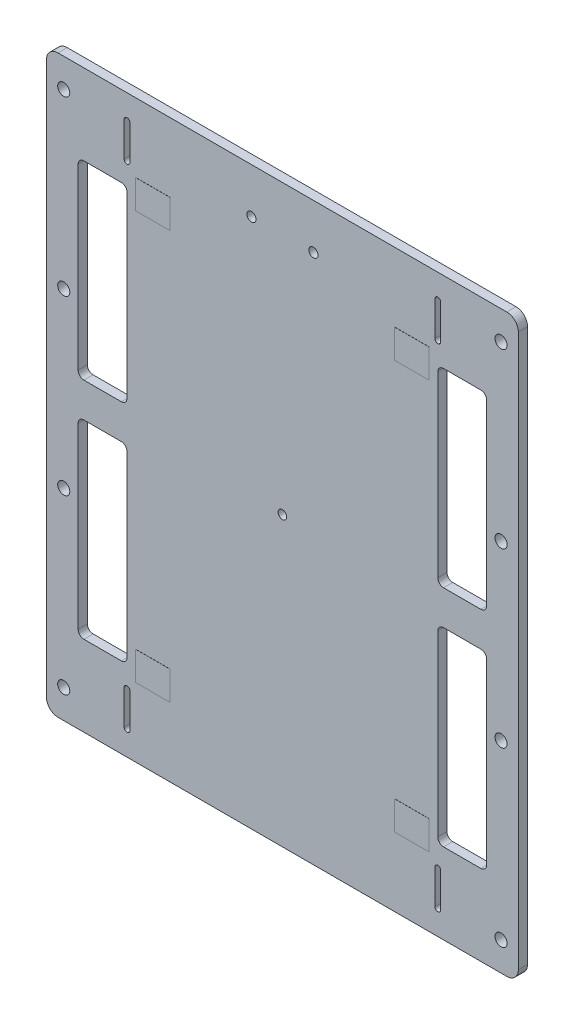
SolidWorks part; units mm, degrees
material "Oshpark board"
ref_plane "Front Plane" through (0, 0, 0) normal (0, 0, 1) x (1, 0, 0)
ref_plane "Top Plane" through (0, 0, 0) normal (0, 1, 0) x (1, 0, 0)
ref_plane "Right Plane" through (0, 0, 0) normal (1, 0, 0) x (0, 0, -1)
sketch "Sketch1" plane through (0, 0, 0) normal (0, 0, 1) x (1, 0, 0)
  line L1 (-39, -50) -> (39, -50)
  line L2 (-41, -48) -> (-41, 48)
  line L3 (-39, 50) -> (39, 50)
  line L4 (41, -48) -> (41, 48)
  line L5 (-41, -50) -> (41, 50) construction
  line L6 (-41, 50) -> (41, -50) construction
  arc A0 (-39, -50) -> (-41, -48) centre (-39, -48) cw
  arc A1 (39, -50) -> (41, -48) centre (39, -48) ccw
  arc A2 (39, 50) -> (41, 48) centre (39, 48) cw
  arc A3 (-41, 48) -> (-39, 50) centre (-39, 48) cw
  point P0 (0, 0)
  dimension "D3" = 2
  dimension "D1" = 100
  dimension "D2" = 82
extrude "Boss-Extrude1" add sketch "Sketch1" along normal blind 1.6
sketch "Sketch2" plane through (0, 0, 1.6) normal (0, 0, 1) x (1, 0, 0)
  line L0 (39, 50) -> (-39, 50) construction
  line L1 (-41, 48) -> (-41, -48) construction
  line L3 (-37.5, 44.2) -> (-37.5, 4.2) construction
  circle A0 centre (0, 0) radius 0.75
  circle A1 centre (-37.5, 44.2) radius 1.05 construction
  circle A2 centre (37.5, 44.2) radius 1.05 construction
  circle A3 centre (37.5, 4.2) radius 1.05 construction
  circle A4 centre (37.5, -35.8) radius 1.05 construction
  circle A5 centre (-37.5, 4.2) radius 1.05 construction
  circle A6 centre (-37.5, -35.8) radius 1.05 construction
  circle A7 centre (-5.38, 42.15) radius 0.8
  circle A8 centre (5.39, 42.15) radius 0.8
  dimension "D1" = 1.5
  dimension "D2" = 2.1
  dimension "D9" = 10.77
  dimension "D7" = 1.6
  dimension "D11" = 7.85
  dimension "D12" = 35.62
  dimension "D3" = 5.8
  dimension "D4" = 3.5
  dimension "D8" = 40
  dimension "D10" = 37.5
  dimension "D5" = 2
  dimension "D6" = 3
extrude "Cut-Extrude1" cut sketch "Sketch2" against normal through all
sketch "Sketch4" plane through (0, 0, 1.6) normal (0, 0, 1) x (1, 0, 0)
  line L0 (-27, 39.75) -> (-27, 45.75) construction
  line L1 (-27.5, 39.75) -> (-27.5, 45.75)
  line L2 (-26.5, 39.75) -> (-26.5, 45.75)
  line L3 (39, 50) -> (-39, 50) construction
  line L4 (-41, 48) -> (-41, -48) construction
  line L5 (27, 39.75) -> (27, 45.75) construction
  line L6 (26.5, 39.75) -> (26.5, 45.75)
  line L7 (27.5, 39.75) -> (27.5, 45.75)
  line L8 (27, -45.75) -> (27, -39.75) construction
  line L9 (26.5, -45.75) -> (26.5, -39.75)
  line L10 (27.5, -45.75) -> (27.5, -39.75)
  line L11 (-27, -45.75) -> (-27, -39.75) construction
  line L12 (-27.5, -45.75) -> (-27.5, -39.75)
  line L13 (-26.5, -45.75) -> (-26.5, -39.75)
  line L14 (-27, 39.75) -> (27, 39.75) construction
  line L15 (-39, -50) -> (39, -50) construction
  arc A0 (-27.5, 39.75) -> (-26.5, 39.75) centre (-27, 39.75) ccw
  arc A1 (-26.5, 45.75) -> (-27.5, 45.75) centre (-27, 45.75) ccw
  arc A2 (26.5, 39.75) -> (27.5, 39.75) centre (27, 39.75) ccw
  arc A3 (27.5, 45.75) -> (26.5, 45.75) centre (27, 45.75) ccw
  arc A4 (26.5, -45.75) -> (27.5, -45.75) centre (27, -45.75) ccw
  arc A5 (27.5, -39.75) -> (26.5, -39.75) centre (27, -39.75) ccw
  arc A6 (-27.5, -45.75) -> (-26.5, -45.75) centre (-27, -45.75) ccw
  arc A7 (-26.5, -39.75) -> (-27.5, -39.75) centre (-27, -39.75) ccw
  point P2 (-27, 42.75)
  point P16 (27, 42.75)
  point P23 (27, -42.75)
  point P30 (-27, -42.75)
  dimension "D1" = 4.25
  dimension "D2" = 13.5
  dimension "D3" = 1
  dimension "D4" = 6
  dimension "D7" = 54
  dimension "D8" = 14
  dimension "D9" = 4.25
  dimension "D10" = 4.25
  dimension "D5" = 2
  dimension "D6" = 2
extrude "Cut-Extrude3" cut sketch "Sketch4" against normal blind 1.6
sketch "Sketch3" plane through (0, 0, 1.6) normal (0, 0, 1) x (1, 0, 0)
  line L1 (-34.5, 36) -> (-28, 36)
  line L2 (-35.5, 35) -> (-35.5, 4)
  line L3 (-34.5, 3) -> (-28, 3)
  line L4 (-27, 35) -> (-27, 4)
  line L5 (-41, 48) -> (-41, -48) construction
  line L6 (41, 0) -> (-41, 0) construction
  line L7 (41, -48) -> (41, 48) construction
  line L8 (-41, 48) -> (-41, -48) construction
  line L9 (0, 50) -> (0, -50) construction
  line L10 (39, 50) -> (-39, 50) construction
  line L11 (-39, -50) -> (39, -50) construction
  line L12 (-34.5, -36) -> (-28, -36)
  line L13 (-35.5, -35) -> (-35.5, -4)
  line L14 (-34.5, -3) -> (-28, -3)
  line L15 (-27, -35) -> (-27, -4)
  line L16 (34.5, -36) -> (28, -36)
  line L17 (27, -35) -> (27, -4)
  line L18 (34.5, -3) -> (28, -3)
  line L20 (35.5, -35) -> (35.5, -4)
  line L21 (34.5, 36) -> (28, 36)
  line L22 (35.5, 35) -> (35.5, 4)
  line L23 (34.5, 3) -> (28, 3)
  line L24 (27, 35) -> (27, 4)
  arc A0 (-35.5, 4) -> (-34.5, 3) centre (-34.5, 4) ccw
  arc A1 (-28, 3) -> (-27, 4) centre (-28, 4) ccw
  arc A2 (-28, 36) -> (-27, 35) centre (-28, 35) cw
  arc A3 (-34.5, 36) -> (-35.5, 35) centre (-34.5, 35) ccw
  arc A5 (-28, -36) -> (-27, -35) centre (-28, -35) ccw
  arc A6 (-34.5, -36) -> (-35.5, -35) centre (-34.5, -35) cw
  arc A7 (-35.5, -4) -> (-34.5, -3) centre (-34.5, -4) cw
  arc A8 (-28, -3) -> (-27, -4) centre (-28, -4) cw
  arc A9 (34.5, -36) -> (35.5, -35) centre (34.5, -35) ccw
  arc A10 (28, -36) -> (27, -35) centre (28, -35) cw
  arc A11 (28, -3) -> (27, -4) centre (28, -4) ccw
  arc A12 (35.5, -4) -> (34.5, -3) centre (34.5, -4) ccw
  arc A13 (28, 36) -> (27, 35) centre (28, 35) ccw
  arc A14 (34.5, 36) -> (35.5, 35) centre (34.5, 35) cw
  arc A15 (35.5, 4) -> (34.5, 3) centre (34.5, 4) cw
  arc A16 (28, 3) -> (27, 4) centre (28, 4) cw
  point P12 (-27, 3)
  point P15 (-27, 36)
  point P18 (-35.5, 36)
  dimension "D5" = 1
  dimension "D1" = 8.5
  dimension "D2" = 33
  dimension "D3" = 14
  dimension "D4" = 5.5
extrude "Cut-Extrude2" cut sketch "Sketch3" against normal through all
sketch "Sketch5" plane through (0, 0, 1.6) normal (0, 0, 1) x (1, 0, 0)
  line L0 (-41, 48) -> (-41, -48) construction
  line L1 (-25.5, 38) -> (-19.5, 38)
  line L2 (-25.5, 38) -> (-25.5, 33)
  line L3 (-25.5, 33) -> (-19.5, 33)
  line L4 (-19.5, 38) -> (-19.5, 33)
  line L5 (39, 50) -> (-39, 50) construction
  line L6 (19.5, 38) -> (19.5, 33)
  line L7 (25.5, 38) -> (25.5, 33)
  line L8 (19.5, 33) -> (25.5, 33)
  line L9 (19.5, 38) -> (25.5, 38)
  line L10 (19.5, -33) -> (19.5, -38)
  line L11 (25.5, -33) -> (25.5, -38)
  line L12 (19.5, -38) -> (25.5, -38)
  line L13 (19.5, -33) -> (25.5, -33)
  line L14 (-25.5, -33) -> (-25.5, -38)
  line L15 (-19.5, -33) -> (-19.5, -38)
  line L16 (-25.5, -38) -> (-19.5, -38)
  line L17 (-25.5, -33) -> (-19.5, -33)
  line L18 (-25.5, 38) -> (19.5, 38) construction
  line L19 (-25.5, 38) -> (-25.5, -33) construction
  dimension "D1" = 5
  dimension "D2" = 6
  dimension "D3" = 15.5
  dimension "D4" = 12
  dimension "D7" = 45
  dimension "D8" = 71
  dimension "D5" = 2
  dimension "D6" = 2
extrude "Boss-Extrude2" add sketch "Sketch5" along normal blind 0.02
hole_wizard "M2 Clearance Hole1" positions "Sketch6" profile "Sketch7" hole size "M2" standard "ANSI Metric" end condition through all
sketch "Sketch6" plane through (0, 0, 0) normal (0, 0, -1) x (-1, 0, 0)
  line L4 (0, -40.934) -> (0, 34.4116) construction
  line L5 (-38, -50) -> (-38, -45) construction
  line L6 (39, -50) -> (-39, -50) construction
  line L7 (-38, -45) -> (-38, -15) construction
  line L8 (-38, -15) -> (-38, 15) construction
  line L9 (-38, 15) -> (-38, 45) construction
  line L10 (-38, 45) -> (-38, 50) construction
  line L11 (-39, 50) -> (39, 50) construction
  line L13 (-41, -48) -> (-41, 48) construction
  point P0 (-38, 45)
  point P27 (-38, -15)
  point P36 (-38, -45)
  point P38 (-38, 15)
  point P58 (0, 0)
  point P59 (38, -45)
  point P60 (38, -15)
  point P61 (38, 15)
  point P62 (38, 45)
  point P63 (-37.5, 37.6723)
  point P64 (-37.5, -35.4835)
  point P65 (-37.5, -43.3994)
  dimension "D1" = 3
  dimension "D2" = 5
sketch "Sketch7" plane through (38, 45, 0) normal (1, 0, 0) x (0, 1, 0)
  line L0 (0, 0) -> (0, 1.62)
  line L1 (0, 1.62) -> (1.05, 1.62)
  line L2 (1.05, 1.62) -> (1.05, 0)
  line L5 (1.05, 0) -> (0, 0)
  line L11 (0, -6.35) -> (0, 107.95) construction
  dimension "Thru Hole Dia." = 2.1
  dimension "Thru Hole Depth" = 1.62
sketch "Sketch8" plane through (0, 0, 1.6) normal (0, 0, 1) x (1, 0, 0)
  line L0 (-15, -11.3) -> (-15, 19.7)
  line L1 (-15, -11.3) -> (-15, 19.7)
  line L2 (12, -14.3) -> (-12, -14.3)
  line L3 (12, -14.3) -> (-12, -14.3)
  line L4 (15, 19.7) -> (15, -11.3)
  line L5 (15, 19.7) -> (15, -11.3)
  line L6 (-12, 22.7) -> (12, 22.7)
  line L7 (-12, 22.7) -> (12, 22.7)
  line L8 (-32.5, 22.7) -> (-21, 22.7)
  line L9 (-32.5, 22.7) -> (-21, 22.7)
  line L10 (-35.5, 19.7) -> (-35.5, -11.3)
  line L11 (-35.5, 19.7) -> (-35.5, -11.3)
  line L12 (-21, -14.3) -> (-32.5, -14.3)
  line L13 (-21, -14.3) -> (-32.5, -14.3)
  line L14 (-18, 19.7) -> (-18, -11.3)
  line L15 (-18, 19.7) -> (-18, -11.3)
  line L16 (18, -11.3) -> (18, 19.7)
  line L17 (18, -11.3) -> (18, 19.7)
  line L18 (32.5, -14.3) -> (21, -14.3)
  line L19 (32.5, -14.3) -> (21, -14.3)
  line L20 (35.5, -11.3) -> (35.5, 19.7)
  line L21 (35.5, -11.3) -> (35.5, 19.7)
  line L22 (21, 22.7) -> (32.5, 22.7)
  line L23 (21, 22.7) -> (32.5, 22.7)
  line L24 (-15, -43) -> (-15, -20.3)
  line L25 (-15, -43) -> (-15, -20.3)
  line L26 (12, -46) -> (-12, -46)
  line L27 (12, -46) -> (-12, -46)
  line L28 (15, -20.3) -> (15, -43)
  line L29 (15, -20.3) -> (15, -43)
  line L30 (-12, -17.3) -> (12, -17.3)
  line L31 (-12, -17.3) -> (12, -17.3)
  line L32 (-35.5, -20.3) -> (-35.5, -43)
  line L33 (-35.5, -20.3) -> (-35.5, -43)
  line L34 (-32.5, -17.3) -> (-21, -17.3)
  line L35 (-32.5, -17.3) -> (-21, -17.3)
  line L36 (-18, -20.3) -> (-18, -43)
  line L37 (-18, -20.3) -> (-18, -43)
  line L38 (-21, -46) -> (-32.5, -46)
  line L39 (-21, -46) -> (-32.5, -46)
  line L40 (18, -43) -> (18, -20.3)
  line L41 (18, -43) -> (18, -20.3)
  line L42 (32.5, -46) -> (21, -46)
  line L43 (32.5, -46) -> (21, -46)
  line L44 (35.5, -43) -> (35.5, -20.3)
  line L45 (35.5, -43) -> (35.5, -20.3)
  line L46 (21, -17.3) -> (32.5, -17.3)
  line L47 (21, -17.3) -> (32.5, -17.3)
  line L48 (-15, 28.7) -> (-15, 42)
  line L49 (-15, 28.7) -> (-15, 42)
  line L50 (12, 25.7) -> (-12, 25.7)
  line L51 (12, 25.7) -> (-12, 25.7)
  line L52 (15, 42) -> (15, 28.7)
  line L53 (15, 42) -> (15, 28.7)
  line L54 (12, 45) -> (-12, 45)
  line L55 (12, 45) -> (-12, 45)
  line L56 (-35.5, 42) -> (-35.5, 28.7)
  line L57 (-35.5, 42) -> (-35.5, 28.7)
  line L58 (-21, 25.7) -> (-32.5, 25.7)
  line L59 (-21, 25.7) -> (-32.5, 25.7)
  line L60 (-18, 42) -> (-18, 28.7)
  line L61 (-18, 42) -> (-18, 28.7)
  line L62 (-21, 45) -> (-32.5, 45)
  line L63 (-21, 45) -> (-32.5, 45)
  line L64 (18, 28.7) -> (18, 42)
  line L65 (18, 28.7) -> (18, 42)
  line L66 (32.5, 25.7) -> (21, 25.7)
  line L67 (32.5, 25.7) -> (21, 25.7)
  line L68 (35.5, 28.7) -> (35.5, 42)
  line L69 (35.5, 28.7) -> (35.5, 42)
  line L70 (32.5, 45) -> (21, 45)
  line L71 (32.5, 45) -> (21, 45)
  line L72 (-32.5, -49) -> (-21, -49)
  line L73 (-32.5, -49) -> (-21, -49)
  line L74 (-12, -49) -> (12, -49)
  line L75 (-12, -49) -> (12, -49)
  line L76 (21, -49) -> (32.5, -49)
  line L77 (21, -49) -> (32.5, -49)
  line L78 (-39, -50) -> (39, -50) construction
  line L79 (41, -48) -> (41, 48) construction
  line L80 (39, 50) -> (-39, 50) construction
  line L81 (-41, 48) -> (-41, -48) construction
  line L82 (-39, -50) -> (39, -50)
  line L83 (41, -48) -> (41, 48)
  line L84 (39, 50) -> (-39, 50)
  line L85 (-41, 48) -> (-41, -48)
  arc A0 (-15, -11.3) -> (-12, -14.3) centre (-12, -11.3) ccw
  arc A1 (-15, -11.3) -> (-12, -14.3) centre (-12, -11.3) ccw
  arc A2 (12, -14.3) -> (15, -11.3) centre (12, -11.3) ccw
  arc A3 (12, -14.3) -> (15, -11.3) centre (12, -11.3) ccw
  arc A4 (15, 19.7) -> (12, 22.7) centre (12, 19.7) ccw
  arc A5 (15, 19.7) -> (12, 22.7) centre (12, 19.7) ccw
  arc A6 (-12, 22.7) -> (-15, 19.7) centre (-12, 19.7) ccw
  arc A7 (-12, 22.7) -> (-15, 19.7) centre (-12, 19.7) ccw
  arc A8 (-18, 19.7) -> (-21, 22.7) centre (-21, 19.7) ccw
  arc A9 (-18, 19.7) -> (-21, 22.7) centre (-21, 19.7) ccw
  arc A10 (-32.5, 22.7) -> (-35.5, 19.7) centre (-32.5, 19.7) ccw
  arc A11 (-32.5, 22.7) -> (-35.5, 19.7) centre (-32.5, 19.7) ccw
  arc A12 (-35.5, -11.3) -> (-32.5, -14.3) centre (-32.5, -11.3) ccw
  arc A13 (-35.5, -11.3) -> (-32.5, -14.3) centre (-32.5, -11.3) ccw
  arc A14 (-21, -14.3) -> (-18, -11.3) centre (-21, -11.3) ccw
  arc A15 (-21, -14.3) -> (-18, -11.3) centre (-21, -11.3) ccw
  arc A16 (18, -11.3) -> (21, -14.3) centre (21, -11.3) ccw
  arc A17 (18, -11.3) -> (21, -14.3) centre (21, -11.3) ccw
  arc A18 (32.5, -14.3) -> (35.5, -11.3) centre (32.5, -11.3) ccw
  arc A19 (32.5, -14.3) -> (35.5, -11.3) centre (32.5, -11.3) ccw
  arc A20 (35.5, 19.7) -> (32.5, 22.7) centre (32.5, 19.7) ccw
  arc A21 (35.5, 19.7) -> (32.5, 22.7) centre (32.5, 19.7) ccw
  arc A22 (21, 22.7) -> (18, 19.7) centre (21, 19.7) ccw
  arc A23 (21, 22.7) -> (18, 19.7) centre (21, 19.7) ccw
  arc A24 (-15, -43) -> (-12, -46) centre (-12, -43) ccw
  arc A25 (-15, -43) -> (-12, -46) centre (-12, -43) ccw
  arc A26 (12, -46) -> (15, -43) centre (12, -43) ccw
  arc A27 (12, -46) -> (15, -43) centre (12, -43) ccw
  arc A28 (15, -20.3) -> (12, -17.3) centre (12, -20.3) ccw
  arc A29 (15, -20.3) -> (12, -17.3) centre (12, -20.3) ccw
  arc A30 (-12, -17.3) -> (-15, -20.3) centre (-12, -20.3) ccw
  arc A31 (-12, -17.3) -> (-15, -20.3) centre (-12, -20.3) ccw
  arc A32 (-32.5, -17.3) -> (-35.5, -20.3) centre (-32.5, -20.3) ccw
  arc A33 (-32.5, -17.3) -> (-35.5, -20.3) centre (-32.5, -20.3) ccw
  arc A34 (-18, -20.3) -> (-21, -17.3) centre (-21, -20.3) ccw
  arc A35 (-18, -20.3) -> (-21, -17.3) centre (-21, -20.3) ccw
  arc A36 (-21, -46) -> (-18, -43) centre (-21, -43) ccw
  arc A37 (-21, -46) -> (-18, -43) centre (-21, -43) ccw
  arc A38 (-35.5, -43) -> (-32.5, -46) centre (-32.5, -43) ccw
  arc A39 (-35.5, -43) -> (-32.5, -46) centre (-32.5, -43) ccw
  arc A40 (18, -43) -> (21, -46) centre (21, -43) ccw
  arc A41 (18, -43) -> (21, -46) centre (21, -43) ccw
  arc A42 (32.5, -46) -> (35.5, -43) centre (32.5, -43) ccw
  arc A43 (32.5, -46) -> (35.5, -43) centre (32.5, -43) ccw
  arc A44 (35.5, -20.3) -> (32.5, -17.3) centre (32.5, -20.3) ccw
  arc A45 (35.5, -20.3) -> (32.5, -17.3) centre (32.5, -20.3) ccw
  arc A46 (21, -17.3) -> (18, -20.3) centre (21, -20.3) ccw
  arc A47 (21, -17.3) -> (18, -20.3) centre (21, -20.3) ccw
  arc A48 (-15, 28.7) -> (-12, 25.7) centre (-12, 28.7) ccw
  arc A49 (-15, 28.7) -> (-12, 25.7) centre (-12, 28.7) ccw
  arc A50 (12, 25.7) -> (15, 28.7) centre (12, 28.7) ccw
  arc A51 (12, 25.7) -> (15, 28.7) centre (12, 28.7) ccw
  arc A52 (15, 42) -> (12, 45) centre (12, 42) ccw
  arc A53 (15, 42) -> (12, 45) centre (12, 42) ccw
  arc A54 (-12, 45) -> (-15, 42) centre (-12, 42) ccw
  arc A55 (-12, 45) -> (-15, 42) centre (-12, 42) ccw
  arc A56 (-35.5, 28.7) -> (-32.5, 25.7) centre (-32.5, 28.7) ccw
  arc A57 (-35.5, 28.7) -> (-32.5, 25.7) centre (-32.5, 28.7) ccw
  arc A58 (-21, 25.7) -> (-18, 28.7) centre (-21, 28.7) ccw
  arc A59 (-21, 25.7) -> (-18, 28.7) centre (-21, 28.7) ccw
  arc A60 (-18, 42) -> (-21, 45) centre (-21, 42) ccw
  arc A61 (-18, 42) -> (-21, 45) centre (-21, 42) ccw
  arc A62 (-32.5, 45) -> (-35.5, 42) centre (-32.5, 42) ccw
  arc A63 (-32.5, 45) -> (-35.5, 42) centre (-32.5, 42) ccw
  arc A64 (18, 28.7) -> (21, 25.7) centre (21, 28.7) ccw
  arc A65 (18, 28.7) -> (21, 25.7) centre (21, 28.7) ccw
  arc A66 (32.5, 25.7) -> (35.5, 28.7) centre (32.5, 28.7) ccw
  arc A67 (32.5, 25.7) -> (35.5, 28.7) centre (32.5, 28.7) ccw
  arc A68 (35.5, 42) -> (32.5, 45) centre (32.5, 42) ccw
  arc A69 (35.5, 42) -> (32.5, 45) centre (32.5, 42) ccw
  arc A70 (21, 45) -> (18, 42) centre (21, 42) ccw
  arc A71 (21, 45) -> (18, 42) centre (21, 42) ccw
  arc A72 (-32.5, -49) -> (-35.5, -52) centre (-32.5, -52) ccw
  arc A73 (-32.5, -49) -> (-34.7361, -50) centre (-32.5, -52) ccw
  arc A74 (-18, -52) -> (-21, -49) centre (-21, -52) ccw
  arc A75 (-18.7639, -50) -> (-21, -49) centre (-21, -52) ccw
  arc A76 (-12, -49) -> (-15, -52) centre (-12, -52) ccw
  arc A77 (-12, -49) -> (-14.2361, -50) centre (-12, -52) ccw
  arc A78 (15, -52) -> (12, -49) centre (12, -52) ccw
  arc A79 (14.2361, -50) -> (12, -49) centre (12, -52) ccw
  arc A80 (21, -49) -> (18, -52) centre (21, -52) ccw
  arc A81 (21, -49) -> (18.7639, -50) centre (21, -52) ccw
  arc A82 (35.5, -52) -> (32.5, -49) centre (32.5, -52) ccw
  arc A83 (34.7361, -50) -> (32.5, -49) centre (32.5, -52) ccw
  arc A84 (-41, -48) -> (-39, -50) centre (-39, -48) ccw construction
  arc A85 (39, -50) -> (41, -48) centre (39, -48) ccw construction
  arc A86 (41, 48) -> (39, 50) centre (39, 48) ccw construction
  arc A87 (-39, 50) -> (-41, 48) centre (-39, 48) ccw construction
  arc A88 (-41, -48) -> (-39, -50) centre (-39, -48) ccw
  arc A89 (39, -50) -> (41, -48) centre (39, -48) ccw
  arc A90 (41, 48) -> (39, 50) centre (39, 48) ccw
  arc A91 (-39, 50) -> (-41, 48) centre (-39, 48) ccw
